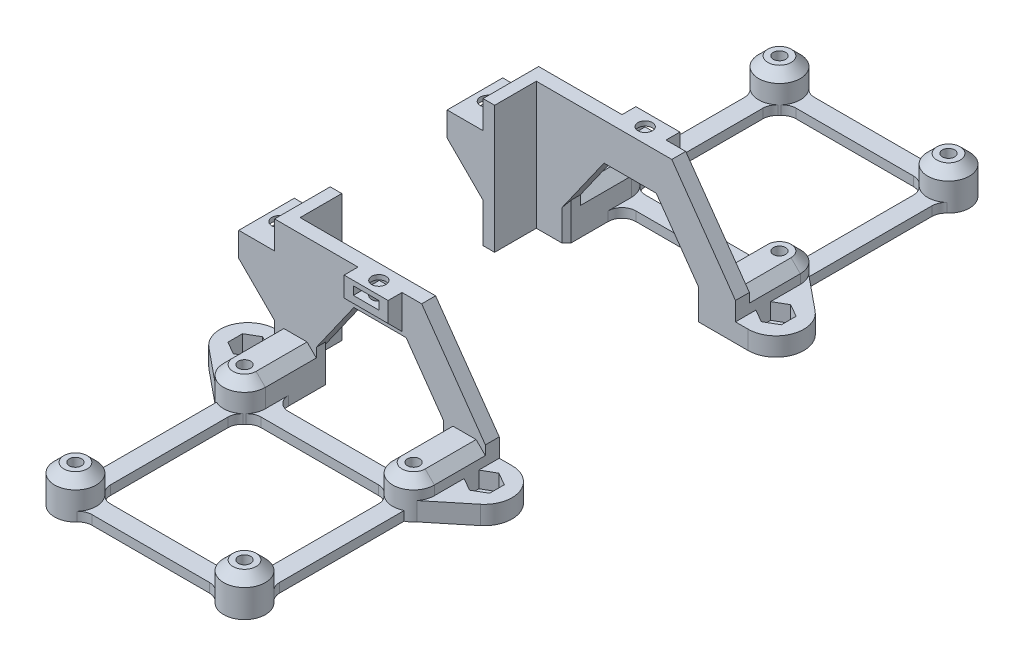
SolidWorks part; units mm, degrees
ref_plane "Front Plane" through (0, 0, 0) normal (0, 0, 1) x (1, 0, 0)
ref_plane "Top Plane" through (0, 0, 0) normal (0, 1, 0) x (1, 0, 0)
ref_plane "Right Plane" through (0, 0, 0) normal (1, 0, 0) x (0, 0, -1)
sketch "Sketch1" plane through (0, 0, 0) normal (0, 1, 0) x (1, 0, 0)
  line L0 (0, 0) -> (-49.6209, 0) construction
  line L1 (-22.75, -39.5) -> (-22.75, -25.5)
  line L2 (-18.25, -39.5) -> (18.25, -39.5) construction
  line L3 (-18.25, -39.5) -> (-18.25, -76) construction
  line L4 (-18.25, -76) -> (18.25, -76) construction
  line L5 (18.25, -39.5) -> (18.25, -76) construction
  line L6 (-22.75, -25.5) -> (-13.75, -25.5)
  line L7 (-13.75, -25.5) -> (-13.75, -39.5)
  line L8 (0, -39.5) -> (0, -76) construction
  line L9 (22.75, -39.5) -> (22.75, -25.5)
  line L10 (13.75, -25.5) -> (13.75, -39.5)
  line L11 (22.75, -25.5) -> (13.75, -25.5)
  circle A2 centre (18.25, -76) radius 4.5
  circle A3 centre (-18.25, -76) radius 4.5
  circle A4 centre (-18.25, -39.5) radius 1.325
  circle A5 centre (18.25, -39.5) radius 1.325
  circle A6 centre (-18.25, -76) radius 1.325
  circle A7 centre (18.25, -76) radius 1.325
  arc A8 (-22.75, -39.5) -> (-13.75, -39.5) centre (-18.25, -39.5) ccw
  arc A9 (22.75, -39.5) -> (13.75, -39.5) centre (18.25, -39.5) cw
  point P7 (0, -39.5)
  dimension "D1" = 9
  dimension "D2" = 2.65
  dimension "D4" = 14
  dimension "D3" = 36.5
  dimension "D5" = 25.5
extrude "Boss-Extrude1" add sketch "Sketch1" along normal blind 8
sketch "Sketch2" plane through (22.75, 0, 0) normal (1, 0, 0) x (0, 0, -1)
  line L0 (-25.5, 0) -> (-25.5, 27.5)
  line L2 (0, 27.5) -> (0, 0) construction
  line L3 (-25.5, 0) -> (-28.5, 0)
  line L4 (-28.5, 0) -> (-28.5, 27.5)
  line L7 (-28.5, 27.5) -> (-25.5, 27.5)
  line L8 (0, 27.5) -> (-25.5, 27.5) construction
  dimension "D1" = 3
  dimension "D2" = 27.5
extrude "Boss-Extrude2" add sketch "Sketch2" against normal up to surface (45.5 mm away) up to face at (-22.75, 4, 32.5)
sketch "Sketch3" plane through (0, 0, 28.5) normal (0, 0, 1) x (1, 0, 0)
  line L0 (-22.75, 8) -> (-9, 27.5) construction
  line L1 (-9, 27.5) -> (9, 27.5) construction
  line L3 (-22.75, 27.5) -> (22.75, 27.5) construction
  line L4 (-22.75, 27.5) -> (-9, 27.5) construction
  line L6 (9, 27.5) -> (22.75, 8)
  line L7 (22.75, 8) -> (22.75, 27.5)
  line L10 (-22.75, 27.5) -> (-22.75, 8) construction
  line L11 (-13.75, 8) -> (-13.75, 0)
  line L12 (-13.75, 0) -> (13.75, 0)
  line L13 (13.75, 0) -> (13.75, 8)
  line L14 (13.75, 8) -> (5.641, 19.5)
  line L15 (5.641, 19.5) -> (-5.641, 19.5)
  line L16 (-5.641, 19.5) -> (-13.75, 8)
  line L17 (22.75, 27.5) -> (9, 27.5)
  point P9 (0, 27.5)
  point P24 (0, 19.5)
  dimension "D1" = 18
  dimension "D2" = 8
extrude "Cut-Extrude1" cut sketch "Sketch3" against normal through all
sketch "Sketch4" plane through (0, 0, 0) normal (0, -1, 0) x (1, 0, 0)
  line L0 (-18.25, 39.5) -> (18.25, 39.5) construction
  line L1 (18.25, 39.5) -> (18.25, 76) construction
  line L2 (-18.25, 76) -> (18.25, 76) construction
  line L3 (-18.25, 39.5) -> (-18.25, 76) construction
  line L4 (-18.25, 39.5) -> (18.25, 39.5) construction
  line L5 (18.25, 39.5) -> (18.25, 76) construction
  line L6 (-18.25, 76) -> (18.25, 76) construction
  line L7 (-18.25, 39.5) -> (-18.25, 76) construction
  line L8 (-20.25, 78) -> (20.25, 78)
  line L9 (20.25, 37.5) -> (20.25, 78)
  line L10 (-20.25, 37.5) -> (20.25, 37.5)
  line L11 (-20.25, 37.5) -> (-20.25, 78)
  line L12 (-16.25, 74) -> (16.25, 74)
  line L13 (16.25, 41.5) -> (16.25, 74)
  line L14 (-16.25, 41.5) -> (16.25, 41.5)
  line L15 (-16.25, 41.5) -> (-16.25, 74)
  dimension "D1" = 2
  dimension "D2" = 2
extrude "Boss-Extrude3" add sketch "Sketch4" against normal blind 2
sketch "Sketch7" plane through (0, 27.5, 0) normal (0, 1, 0) x (1, 0, 0)
  line L0 (-22.75, -25.5) -> (9, -25.5) construction
  line L1 (-2.75, -26) -> (2.75, -26) construction
  line L2 (-2.75, -26) -> (-2.75, -31.5) construction
  line L3 (-2.75, -31.5) -> (2.75, -31.5) construction
  line L4 (2.75, -26) -> (2.75, -31.5) construction
  line L5 (-22.75, -28.5) -> (9, -28.5) construction
  line L6 (-4.75, -28.5) -> (4.75, -28.5)
  line L7 (-4.75, -28.5) -> (-4.75, -31.5)
  line L8 (-4.75, -31.5) -> (4.75, -31.5)
  line L9 (4.75, -28.5) -> (4.75, -31.5)
  point P4 (0, -26)
  point P14 (0, -28.5)
  dimension "D1" = 5.5
  dimension "D2" = 0.5
  dimension "D3" = 2
extrude "Boss-Extrude5" add sketch "Sketch7" against normal blind 4.3
sketch "Sketch8" plane through (0, 27.5, 0) normal (0, 1, 0) x (1, 0, 0)
  line L1 (-2.75, -26) -> (2.75, -26)
  line L2 (-2.75, -26) -> (-2.75, -31.5)
  line L3 (-2.75, -31.5) -> (2.75, -31.5)
  line L4 (2.75, -26) -> (2.75, -31.5)
extrude "Cut-Extrude3" cut sketch "Sketch8" against normal blind 1.8 from offset 1 offset against normal yes
chamfer "Chamfer3" distance 3 angle 45 1 edges at (0, 23.2, 28.5)
sketch "Sketch9" plane through (0, 27.5, 0) normal (0, 1, 0) x (1, 0, 0)
  line L0 (-2.75, -26) -> (-2.75, -31.5) construction
  line L1 (-2.75, -26) -> (2.75, -26) construction
  circle A0 centre (0, -28.75) radius 1.55
  point P5 (-2.75, -28.75)
  point P8 (0, -26)
  dimension "D1" = 3.1
extrude "Cut-Extrude4" cut sketch "Sketch9" against normal blind 5.4
sketch "Sketch10" plane through (0, 0, 0) normal (0, -1, 0) x (1, 0, 0)
  line L0 (-22.75, 25.5) -> (-25.5, 25.5)
  line L1 (-25.5, 28.3246) -> (-22.75, 29.9123)
  line L2 (-22.75, 29.9123) -> (-22.75, 33.0877)
  line L3 (-22.75, 33.0877) -> (-25.5, 34.6754)
  line L4 (-25.5, 34.6754) -> (-28.25, 33.0877)
  line L5 (-28.25, 33.0877) -> (-28.25, 29.9123)
  line L6 (-28.25, 29.9123) -> (-25.5, 28.3246)
  line L7 (-22.75, 25.5) -> (-22.75, 39.5) construction
  line L8 (-20.25, 43.5311) -> (-29.2943, 36.1479)
  line L10 (-20.25, 43.5311) -> (-20.25, 25.5)
  line L11 (-13.75, 25.5) -> (-22.75, 25.5) construction
  line L12 (-20.25, 25.5) -> (-22.75, 25.5)
  circle A0 centre (-25.5, 31.5) radius 2.75 construction
  arc A2 (-25.5, 25.5) -> (-29.2943, 36.1479) centre (-25.5, 31.5) cw
  dimension "D2" = 6
  dimension "D1" = 5.5
extrude "Boss-Extrude6" add sketch "Sketch10" against normal blind 4
sketch "Sketch11" plane through (0, 0, 0) normal (0, -1, 0) x (1, 0, 0)
  line L1 (-28.25, 33.0877) -> (-28.25, 29.9123) construction
  line L2 (-28.25, 29.9123) -> (-25.5, 28.3246) construction
  line L3 (-25.5, 28.3246) -> (-22.75, 29.9123) construction
  line L4 (-22.75, 29.9123) -> (-22.75, 33.0877) construction
  line L5 (-22.75, 33.0877) -> (-25.5, 34.6754) construction
  line L6 (-25.5, 34.6754) -> (-28.25, 33.0877) construction
  line L7 (-28.25, 33.0877) -> (-28.25, 29.9123)
  line L8 (-28.25, 29.9123) -> (-25.5, 28.3246)
  line L9 (-25.5, 28.3246) -> (-22.75, 29.9123)
  line L10 (-22.75, 29.9123) -> (-22.75, 33.0877)
  line L11 (-22.75, 33.0877) -> (-25.5, 34.6754)
  line L12 (-25.5, 34.6754) -> (-28.25, 33.0877)
  circle A1 centre (-25.5, 31.5) radius 1.5
  dimension "D1" = 3
extrude "Boss-Extrude7" add sketch "Sketch11" against normal blind 0.5
mirror "Mirror1" about plane through (0, 0, 0) normal (1, 0, 0) of "Boss-Extrude7", "Boss-Extrude6"
fillet "Fillet2" radius 3 14 edges at (-13.75, 1, 37.5) (13.75, 1, 37.5) (-20.25, 1, 71.9689) (20.25, 1, 71.9689) (14.2189, 1, 78) (-14.2189, 1, 78) (16.25, 1, 71.9689) (14.2189, 1, 74) (16.25, 1, 43.5311) (14.2189, 1, 41.5) (-16.25, 1, 71.9689) (-14.2189, 1, 74) (-14.2189, 1, 41.5) (-16.25, 1, 43.5311)
chamfer "Chamfer4" distance 1 angle 45 2 edges at (13.75, 4, 25.5) (-13.75, 4, 25.5)
sketch "Sketch12" plane through (0, 0, 25.5) normal (0, 0, -1) x (-1, 0, 0)
  line L0 (14.75, 0) -> (25.5, 0) construction
  line L1 (22.75, 27.5) -> (20.25, 27.5)
  line L2 (22.75, 27.5) -> (22.75, 0)
  line L3 (22.75, 0) -> (20.25, 0)
  line L4 (20.25, 27.5) -> (20.25, 0)
  dimension "D1" = 2.5
extrude "Boss-Extrude8" add sketch "Sketch12" along normal blind 9
chamfer "Chamfer5" distance 2 angle 45 8 edges at (18.25, 8, 80.5) (13.75, 8, 34) (22.75, 8, 34) (18.25, 8, 44) (-22.75, 8, 34) (-13.75, 8, 34) (-18.25, 8, 44) (-18.25, 8, 80.5)
mirror "Mirror3" about plane through (0, 0, 0) normal (0, 0, 1) of bodies 128 126
ref_plane "Plane1" through (0, 21.5, 0) normal (0, 1, 0) x (1, 0, 0)
sketch "Sketch13" plane through (0, 21.5, 0) normal (0, 1, 0) x (1, 0, 0)
  line L0 (-25, -19.75) -> (-30.5, -19.75) construction
  line L5 (-22.75, -16.5) -> (-30.5, -16.5)
  line L6 (-22.75, -16.5) -> (-22.75, -28.5)
  line L7 (-22.75, -28.5) -> (-30.5, -28.5)
  line L8 (-30.5, -16.5) -> (-30.5, -28.5)
  line L9 (-30.5, -19.75) -> (-30.5, -25.25) construction
  line L10 (-30.5, -25.25) -> (-25, -25.25) construction
  line L11 (0, 0) -> (-10.2421, 0) construction
  line L12 (-30.5, 25.25) -> (-25, 25.25) construction
  line L13 (-30.5, 19.75) -> (-30.5, 25.25) construction
  line L14 (-25, 19.75) -> (-30.5, 19.75) construction
  line L15 (-30.5, 16.5) -> (-30.5, 28.5)
  line L16 (-22.75, 28.5) -> (-30.5, 28.5)
  line L17 (-22.75, 16.5) -> (-22.75, 28.5)
  line L18 (-22.75, 16.5) -> (-30.5, 16.5)
  line L19 (-25, -19.75) -> (-25, -25.25) construction
  line L20 (-27.75, -19.75) -> (-27.75, -25.25) construction
  point P9 (-30.5, -22.5)
  point P10 (-30.5, -22.5)
  dimension "D1" = 5.5
  dimension "D2" = 5
extrude "Boss-Extrude9" add sketch "Sketch13" against normal blind 5
sketch "Sketch14" plane through (0, 21.5, 0) normal (0, 1, 0) x (1, 0, 0)
  line L0 (-30.5, 16.5) -> (-30.5, 28.5) construction
  line L1 (-25, 19.75) -> (-30.5, 19.75)
  line L2 (-25, 19.75) -> (-25, 25.25)
  line L3 (-25, 25.25) -> (-30.5, 25.25)
  line L4 (-30.5, 19.75) -> (-30.5, 25.25)
  line L5 (-30.5, -16.5) -> (-30.5, -28.5) construction
  line L6 (-25, -25.25) -> (-30.5, -25.25)
  line L7 (-25, -25.25) -> (-25, -19.75)
  line L8 (-25, -19.75) -> (-30.5, -19.75)
  line L9 (-30.5, -25.25) -> (-30.5, -19.75)
extrude "Cut-Extrude5" cut sketch "Sketch14" against normal blind 1.8 from offset 1 offset against normal yes
chamfer "Chamfer6" distance 8 angle 45 1 edges at (-22.75, 16.5, 22.5)
chamfer "Chamfer7" distance 8 angle 45 1 edges at (-22.75, 16.5, -22.5)
sketch "Sketch15" plane through (0, 21.5, 0) normal (0, 1, 0) x (1, 0, 0)
  line L0 (-30.5, -19.75) -> (-25, -25.25) construction
  line L1 (0, 0) -> (-17.1172, 0) construction
  circle A0 centre (-27.75, -22.5) radius 1.6
  circle A1 centre (-27.75, 22.5) radius 1.6
  dimension "D1" = 3.2
extrude "Cut-Extrude6" cut sketch "Sketch15" against normal blind 12
sketch "Sketch17" plane through (0, 0, 31.5) normal (0, 0, 1) x (1, 0, 0)
  line L4 (2.75, 26.5) -> (-2.75, 26.5)
  line L5 (-2.75, 26.5) -> (-2.75, 24.7)
  line L6 (-2.75, 24.7) -> (2.75, 24.7)
  line L7 (2.75, 24.7) -> (2.75, 26.5)
  line L8 (2.75, 26.5) -> (-2.75, 26.5)
  line L9 (-2.75, 26.5) -> (-2.75, 24.7)
  line L10 (-2.75, 24.7) -> (2.75, 24.7)
  line L11 (2.75, 24.7) -> (2.75, 26.5)
  dimension "D1" = 0
extrude "Cut-Extrude8" cut sketch "Sketch17" against normal blind 5.6
sketch "Sketch18" plane through (-30.5, 0, 0) normal (-1, 0, 0) x (0, 0, 1)
  line L1 (19.75, 20.5) -> (25.25, 20.5)
  line L2 (19.75, 20.5) -> (19.75, 18.7)
  line L3 (19.75, 18.7) -> (25.25, 18.7)
  line L4 (25.25, 20.5) -> (25.25, 18.7)
extrude "Cut-Extrude9" cut sketch "Sketch18" against normal blind 5.6
sketch "Sketch19" plane through (-30.5, 0, 0) normal (-1, 0, 0) x (0, 0, 1)
  line L1 (-25.25, 20.5) -> (-19.75, 20.5)
  line L2 (-25.25, 20.5) -> (-25.25, 18.7)
  line L3 (-25.25, 18.7) -> (-19.75, 18.7)
  line L4 (-19.75, 20.5) -> (-19.75, 18.7)
extrude "Cut-Extrude10" cut sketch "Sketch19" against normal blind 5.6
sketch "Sketch20" plane through (0, 0, -31.5) normal (0, 0, -1) x (-1, 0, 0)
  line L1 (-2.75, 26.5) -> (2.75, 26.5)
  line L2 (-2.75, 26.5) -> (-2.75, 24.7)
  line L3 (-2.75, 24.7) -> (2.75, 24.7)
  line L4 (2.75, 26.5) -> (2.75, 24.7)
extrude "Cut-Extrude11" cut sketch "Sketch20" against normal blind 5.6
sketch "Sketch21" plane through (0, 0, 0) normal (0, 1, 0) x (1, 0, 0)
  line L1 (-67.789, 96.7385) -> (53.7779, 96.7385)
  line L2 (-67.789, 96.7385) -> (-67.789, 5.0481)
  line L3 (-67.789, 5.0481) -> (53.7779, 5.0481)
  line L4 (53.7779, 96.7385) -> (53.7779, 5.0481)
extrude "Cut-Extrude13" [suppressed] cut sketch "Sketch21" along normal through all flip side to cut
